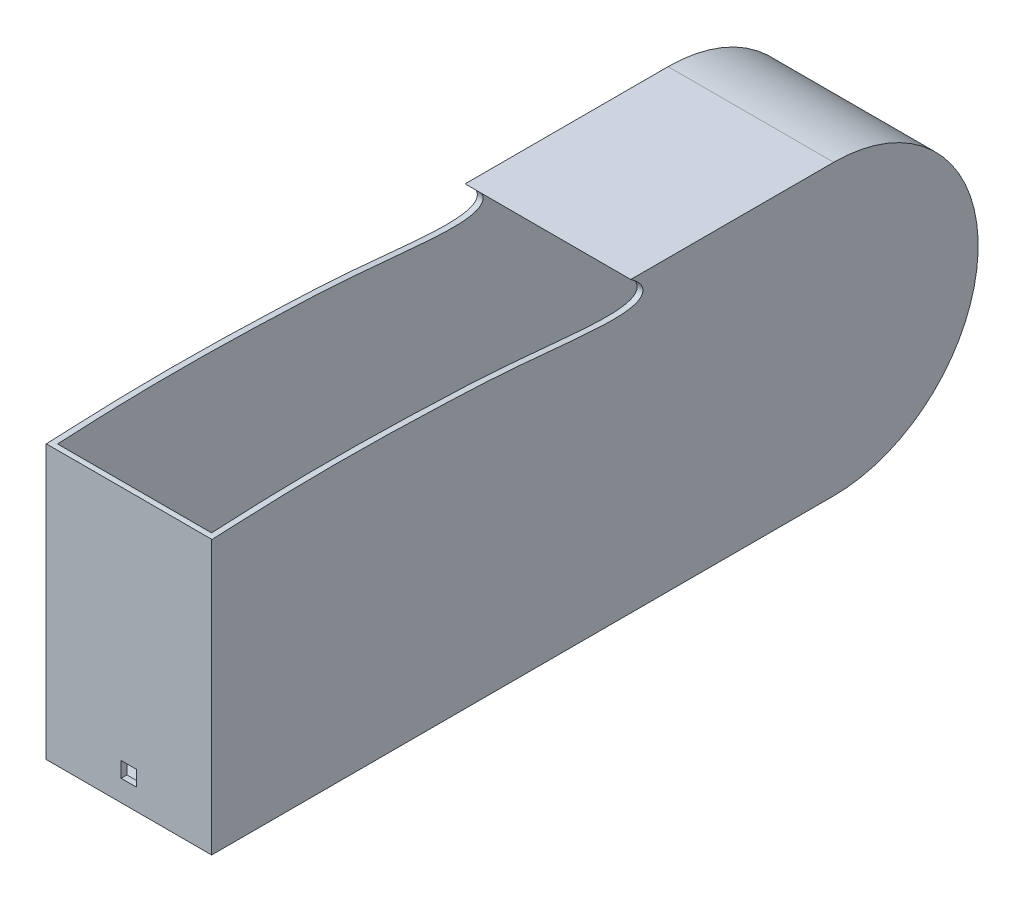
SolidWorks part; units mm, degrees
other "Markup1"
sketch "Sketch10" plane through (68.2625, 233.3625, 398.4625) normal (0.4688, 0.3088, 0.8276) x (0.8055, 0.235, -0.5439)
material "Thornel Mat VMA Foam Core (2)"
ref_plane "Front Plane" through (0, 0, 0) normal (0, 0, 1) x (1, 0, 0)
ref_plane "Top Plane" through (0, 0, 0) normal (0, 1, 0) x (1, 0, 0)
ref_plane "Right Plane" through (0, 0, 0) normal (1, 0, 0) x (0, 0, -1)
sketch "Sketch2" plane through (0, 0, 0) normal (1, 0, 0) x (0, 0, -1)
  line L0 (0, 0) -> (-508, 0)
  line L1 (-508, 0) -> (-508, 228.6)
  line L2 (-508, 228.6) -> (0, 228.6)
  line L4 (0, -4.7625) -> (-512.7625, -4.7625)
  line L5 (-512.7625, -4.7625) -> (-512.7625, 233.3625)
  line L6 (-512.7625, 233.3625) -> (0, 233.3625)
  arc A0 (0, 0) -> (0, 228.6) centre (0, 114.3) ccw
  arc A1 (0, -4.7625) -> (0, 233.3625) centre (0, 114.3) ccw
  dimension "D1" = 228.6
  dimension "D3" = 508
  dimension "D2" = 4.7625
extrude "Boss-Extrude1" add sketch "Sketch2" along normal blind 63.5 and the other way blind 63.5
sketch "Sketch4" plane through (0, 0, 512.7625) normal (0, 0, 1) x (1, 0, 0)
  line L0 (0, -132.0971) -> (0, 132.0971) construction
  line L2 (-6.35, 25.4) -> (6.35, 25.4)
  line L3 (75.0888, 0) -> (-75.0888, 0) construction
  line L4 (-6.35, 25.4) -> (-6.35, 12.7)
  line L5 (-6.35, 12.7) -> (6.35, 12.7)
  line L6 (6.35, 25.4) -> (6.35, 12.7)
  dimension "D3" = 12.7
  dimension "D4" = 12.7
  dimension "D5" = 12.7
  dimension "D6" = 6.35
extrude "Cut-Extrude1" cut sketch "Sketch4" against normal up to next
sketch "Sketch9" plane through (63.5, 0, 0) normal (1, 0, 0) x (0, 0, -1)
  line L0 (0, 75.0888) -> (0, -75.0888) construction
  line L1 (-512.7625, 233.3625) -> (0, 233.3625)
  line L2 (-512.7625, 233.3625) -> (-512.7625, -4.7625)
  line L3 (-512.7625, -4.7625) -> (0, -4.7625)
  arc A0 (0, -4.7625) -> (0, 233.3625) centre (0, 114.3) ccw
  arc A1 (0, -4.7625) -> (0, 233.3625) centre (0, 114.3) ccw construction
extrude "Boss-Extrude3" add sketch "Sketch9" along normal blind 4.7625
mirror "Mirror1" about plane through (0, 0, 0) normal (1, 0, 0) of "Boss-Extrude3"
curve "Curve4"
  spline degree 3 poles (0, 0.0315, 25.4063) (0, 0.0393, 25.3837) (0, 0.0703, 25.2937) (0, 0.1399, 25.0921) (0, 0.2522, 24.7577) (0, 0.405, 24.2942) (0, 0.5921, 23.7055) (0, 0.8077, 22.997) (0, 1.0451, 22.1758) (0, 1.2966, 21.2496) (0, 1.5548, 20.228) (0, 1.8116, 19.121) (0, 2.0603, 17.9406) (0, 2.2931, 16.6991) (0, 2.5029, 15.4099) (0, 2.6845, 14.087) (0, 2.832, 12.7455) (0, 2.9406, 11.3997) (0, 3.012, 10.0556) (0, 3.0204, 8.7276) (0, 2.9555, 7.4344) (0, 2.8238, 6.2027) (0, 2.6331, 5.0487) (0, 2.3917, 3.9878) (0, 2.1114, 3.0332) (0, 1.8047, 2.1961) (0, 1.4841, 1.4854) (0, 1.1619, 0.9079) (0, 0.8495, 0.4662) (0, 0.5537, 0.1626) (0, 0.2735, -0.0122) (0, -0.0084, -0.028) (0, -0.2343, 0.1391) (0, -0.3758, 0.4322) (0, -0.4687, 0.835) (0, -0.5173, 1.354) (0, -0.5271, 1.984) (0, -0.502, 2.719) (0, -0.4482, 3.5507) (0, -0.3722, 4.4705) (0, -0.2826, 5.4695) (0, -0.187, 6.5387) (0, -0.0938, 7.6688) (0, -0.0116, 8.8505) (0, 0.0504, 10.0833) (0, 0.0941, 11.3564) (0, 0.1392, 12.6563) (0, 0.1753, 13.9604) (0, 0.2014, 15.2542) (0, 0.216, 16.5239) (0, 0.2186, 17.7555) (0, 0.21, 18.9353) (0, 0.192, 20.05) (0, 0.1653, 21.0867) (0, 0.1345, 22.0333) (0, 0.1002, 22.8789) (0, 0.0674, 23.6118) (0, 0.0327, 24.228) (0, 0.0159, 24.706) (0, -0.0269, 25.0741) (0, -0.0004, 25.2565) (0, -0.052, 25.3969) (0, -0.0123, 25.3993) (0, 0, 25.4) knots 0 0 0 0 0.001372 0.005465 0.012235 0.021602 0.033461 0.047671 0.064081 0.082496 0.102719 0.124527 0.147676 0.171913 0.196978 0.222597 0.248497 0.274385 0.300041 0.32569 0.350525 0.37428 0.396711 0.417577 0.436654 0.453744 0.46868 0.481329 0.491631 0.499616 0.505546 0.510185 0.514824 0.520702 0.528516 0.538466 0.550543 0.564643 0.580638 0.598345 0.617584 0.638174 0.659922 0.682632 0.706121 0.730727 0.7557 0.780732 0.805564 0.829932 0.85357 0.876213 0.89761 0.917519 0.935698 0.951943 0.966047 0.97784 0.987174 0.993932 0.998018 0.999386 1 1 1 1
sketch "Sketch11" plane through (0, 0, 0) normal (1, 0, 0) x (0, 0, -1)
  line L0 (-512.7625, 220.6625) -> (-512.8494, 221.1035)
  line L1 (-512.7625, 220.6625) -> (-157.2494, 220.6625) construction
  line L2 (-157.2494, 220.6625) -> (-157.2494, -4.859) construction
  line L5 (0, 233.3625) -> (-512.7625, 233.3625) construction
  spline S1 degree 3 poles (-512.8494, 221.1035) (-512.5327, 221.211) (-511.2709, 221.6395) (-508.4464, 222.6005) (-503.763, 224.1503) (-497.27, 226.2597) (-489.0232, 228.8414) (-479.1, 231.8139) (-467.598, 235.0832) (-454.628, 238.5453) (-440.3211, 242.0946) (-424.8214, 245.6175) (-408.2949, 249.0248) (-390.9145, 252.2043) (-372.8679, 255.0613) (-354.3533, 257.5202) (-335.5792, 259.5005) (-316.7471, 260.9376) (-297.9418, 261.8532) (-279.3661, 261.8892) (-261.2801, 260.9024) (-244.0588, 258.985) (-227.9296, 256.2468) (-213.1045, 252.8051) (-199.7687, 248.8255) (-188.0775, 244.4846) (-178.1562, 239.9564) (-170.0982, 235.4141) (-163.9386, 231.0172) (-159.7101, 226.8608) (-157.2829, 222.9313) (-157.0786, 218.9863) (-159.4304, 215.8367) (-163.5377, 213.876) (-169.1785, 212.6017) (-176.4414, 211.9526) (-185.2545, 211.8549) (-195.5336, 212.2509) (-207.1634, 213.0536) (-220.0247, 214.1735) (-233.9932, 215.4886) (-248.9432, 216.8909) (-264.7457, 218.2642) (-281.27, 219.4865) (-298.5113, 220.4285) (-316.3158, 221.1186) (-334.4958, 221.8293) (-352.7357, 222.4132) (-370.8319, 222.8575) (-388.5916, 223.14) (-405.8192, 223.252) (-422.3225, 223.2033) (-437.9156, 223.0206) (-452.4184, 222.7108) (-465.6607, 222.3381) (-477.4914, 221.909) (-487.7448, 221.4958) (-496.3662, 221.0477) (-503.0536, 220.8417) (-508.2056, 220.2665) (-510.7559, 220.6486) (-512.723, 219.9346) (-512.7531, 220.4902) (-512.7625, 220.6625) knots 0 0 0 0 0.001372 0.005465 0.012235 0.021602 0.033461 0.047671 0.064081 0.082496 0.102719 0.124527 0.147676 0.171913 0.196978 0.222597 0.248497 0.274385 0.300041 0.32569 0.350525 0.37428 0.396711 0.417577 0.436654 0.453744 0.46868 0.481329 0.491631 0.499616 0.505546 0.510185 0.514824 0.520702 0.528516 0.538466 0.550543 0.564643 0.580638 0.598345 0.617584 0.638174 0.659922 0.682632 0.706121 0.730727 0.7557 0.780732 0.805564 0.829932 0.85357 0.876213 0.89761 0.917519 0.935698 0.951943 0.966047 0.97784 0.987174 0.993932 0.998018 0.999386 1 1 1 1
  dimension "D1" = 355.6
  dimension "D2" = 12.7
extrude "Cut-Extrude2" cut sketch "Sketch11" against normal up to next and the other way up to next contours S1 L0
sketch "Sketch12" plane through (-68.2625, 0, 0) normal (-1, 0, 0) x (0, 0, 1)
  line L2 (512.7625, 221.133) -> (512.7625, 233.3625)
  line L3 (512.7625, 233.3625) -> (473.6238, 233.3625)
  line L4 (512.7625, 221.133) -> (512.7625, 233.3625)
  line L5 (512.7625, 233.3625) -> (473.6238, 233.3625)
  spline S1 degree 3 poles (-508.9977, -1215.4577) (-662.1122, 33.0975) (-15.2014, 379.8817) (489.0232, 228.8414) (497.27, 226.2597) (503.763, 224.1503) (508.4464, 222.6005) (623.0348, 183.6156) (737.8386, 150.5383) (234.453, -1748.2205) knots -2.123775 -2.123775 -2.123775 -2.123775 0.008638 0.022848 0.034707 0.044074 0.050844 0.054938 0.540437 0.540437 0.540437 0.540437 only from (473.6238, 233.3625) to (512.7625, 221.133)
  spline S2 degree 3 poles (473.6238, 233.3625) (475.6206, 232.7955) (480.9449, 231.2612) (489.0232, 228.8414) (497.27, 226.2597) (503.763, 224.1503) (508.4464, 222.6005) (511.2419, 221.6494) (512.4748, 221.2307) (512.7625, 221.133) knots 0.000125 0.000125 0.000125 0.000125 0.008638 0.022848 0.034707 0.044074 0.050844 0.054938 0.056184 0.056184 0.056184 0.056184
  dimension "D1" = 0
extrude "Cut-Extrude3" cut sketch "Sketch12" against normal up to next (136.525 mm away)
ref_plane "Plane1" through (0, 220.6625, 0) normal (0, 1, 0) x (1, 0, 0)
equation "\"fuselage_height\"=9"
equation "\"D1@Sketch2\"=\"fuselage_height\""
equation "\"fuselage_length\" = 20"
equation "\"D3@Sketch2\"= \"fuselage_length\""
